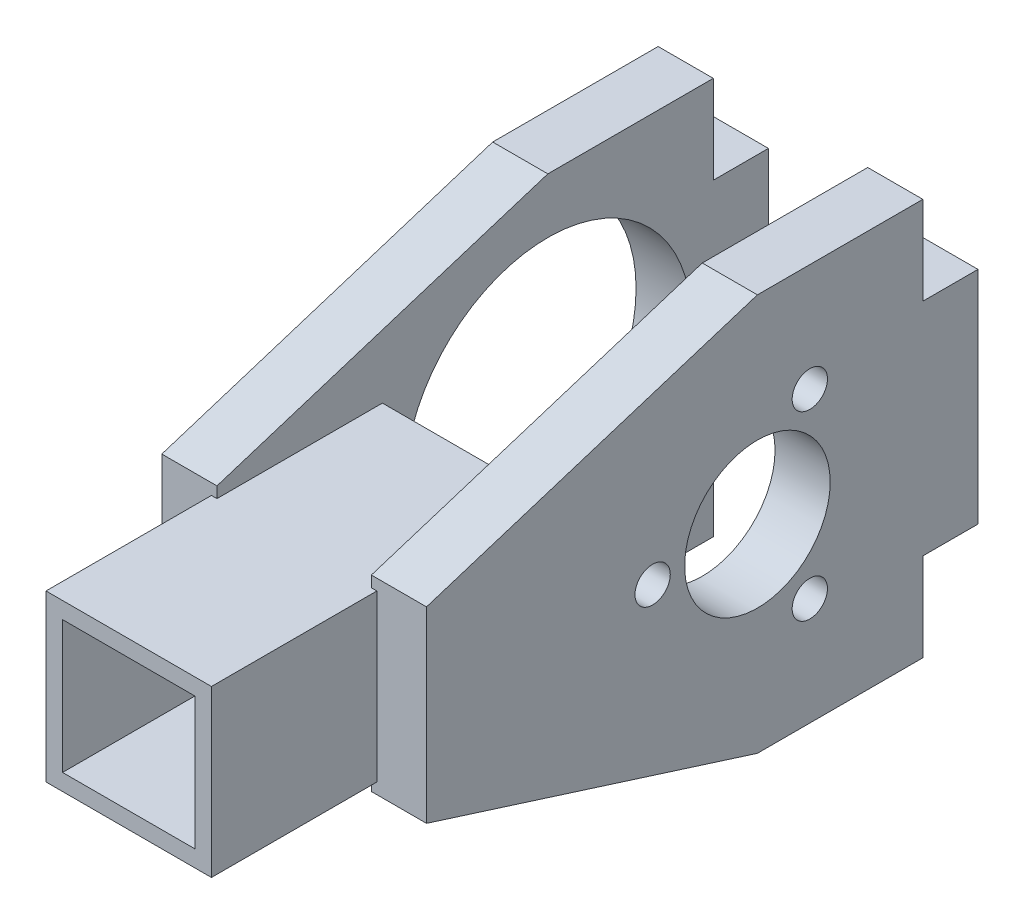
SolidWorks part; units mm, degrees
ref_plane "正面" through (0, 0, 0) normal (0, 0, 1) x (1, 0, 0)
ref_plane "平面" through (0, 0, 0) normal (0, 1, 0) x (1, 0, 0)
ref_plane "右側面" through (0, 0, 0) normal (1, 0, 0) x (0, 0, -1)
sketch "ｽｹｯﾁ1" plane through (0, 0, 0) normal (0, 0, 1) x (1, 0, 0)
  circle A0 centre (0, 0) radius 23.5 construction
  circle A1 centre (0, 0) radius 20 construction
  circle A2 centre (0, 20) radius 1.6 construction
  circle A3 centre (20, 0) radius 1.6 construction
  circle A4 centre (0, -20) radius 1.6 construction
  circle A5 centre (-20, 0) radius 1.6 construction
  point P15 (0, 0)
  dimension "D1" = 40
  dimension "47" = 47
  dimension "D2" = 3.2
  dimension "D3" = 4
ref_plane "arm_link1_m2006_mount_surface" through (7, 0, 0) normal (1, 0, 0) x (0, 0, -1)
ref_plane "arm_link1_axis_hold_mount_surface" through (-7, 0, 0) normal (1, 0, 0) x (0, 0, -1)
sketch "ｽｹｯﾁ3" plane through (7, 0, 0) normal (1, 0, 0) x (0, 0, -1)
  line L0 (0, 0) -> (-45, 0) construction
  line L1 (5, 10) -> (5, -10)
  line L2 (5, -10) -> (0, -10)
  line L3 (0, -10) -> (0, -18)
  line L4 (0, -18) -> (-15, -18)
  line L5 (-15, -18) -> (-45, -8.5)
  line L6 (-45, -8.5) -> (-45, 8.5)
  line L7 (-15, 18) -> (-45, 8.5)
  line L8 (0, 18) -> (-15, 18)
  line L9 (0, 10) -> (0, 18)
  line L10 (5, 10) -> (0, 10)
  circle A0 centre (-15, 0) radius 9.5 construction
  circle A1 centre (-15, 0) radius 6.6
  circle A2 centre (-24.5, 0) radius 1.6
  circle A3 centre (-10.25, 8.2272) radius 1.6
  circle A4 centre (-10.25, -8.2272) radius 1.6
  point P17 (5, 0)
  point P26 (-15, 0)
  dimension "D7" = 19
  dimension "D8" = 13.2
  dimension "D9" = 3.2
  dimension "D1" = 8.5
  dimension "D2" = 10
  dimension "D3" = 8
  dimension "D4" = 15
  dimension "D5" = 45
  dimension "D6" = 5
  dimension "D10" = 3
extrude "ﾎﾞｽ - 押し出し1" add sketch "ｽｹｯﾁ3" along normal blind 5
sketch "ｽｹｯﾁ5" plane through (-7, 0, 0) normal (1, 0, 0) x (0, 0, -1)
  line L0 (0, 0) -> (-53.7832, 0) construction
  line L1 (-45, -8.5) -> (-45, 8.5)
  line L2 (-45, 8.5) -> (-15, 18)
  line L3 (-15, 18) -> (0, 18)
  line L4 (0, 18) -> (0, 10)
  line L5 (0, 10) -> (5, 10)
  line L6 (5, 10) -> (5, -10)
  line L8 (-45, 8.5) -> (-45, -8.5) construction
  line L9 (0, -10) -> (5, -10)
  line L10 (0, -18) -> (0, -10)
  line L11 (-15, -18) -> (0, -18)
  line L12 (-45, -8.5) -> (-15, -18)
  circle A0 centre (-15, 0) radius 13
  point P19 (5, 0)
  point P23 (-45, 0)
  dimension "D6" = 26
  dimension "D1" = 5
  dimension "D2" = 10
  dimension "D3" = 8
  dimension "D4" = 8.5
  dimension "D5" = 15
extrude "ﾎﾞｽ - 押し出し2" add sketch "ｽｹｯﾁ5" against normal blind 5 separate body
sketch "ｽｹｯﾁ6" plane through (0, 0, 45) normal (0, 0, 1) x (1, 0, 0)
  line L1 (7.5, -7.5) -> (-7.5, -7.5)
  line L2 (7.5, -7.5) -> (7.5, 7.5)
  line L3 (7.5, 7.5) -> (-7.5, 7.5)
  line L4 (-7.5, -7.5) -> (-7.5, 7.5)
  line L6 (0, -25.85) -> (0, 25.85) construction
  line L7 (25.85, 0) -> (-25.85, 0) construction
  line L8 (6, -6) -> (-6, -6)
  line L9 (-6, -6) -> (-6, 6)
  line L10 (6, 6) -> (-6, 6)
  line L11 (6, -6) -> (6, 6)
  dimension "D1" = 15
  dimension "D2" = 7.5
  dimension "D3" = 7.5
  dimension "D4" = 1.5
extrude "ﾎﾞｽ - 押し出し3" add sketch "ｽｹｯﾁ6" against normal blind 15 and the other way blind 15
